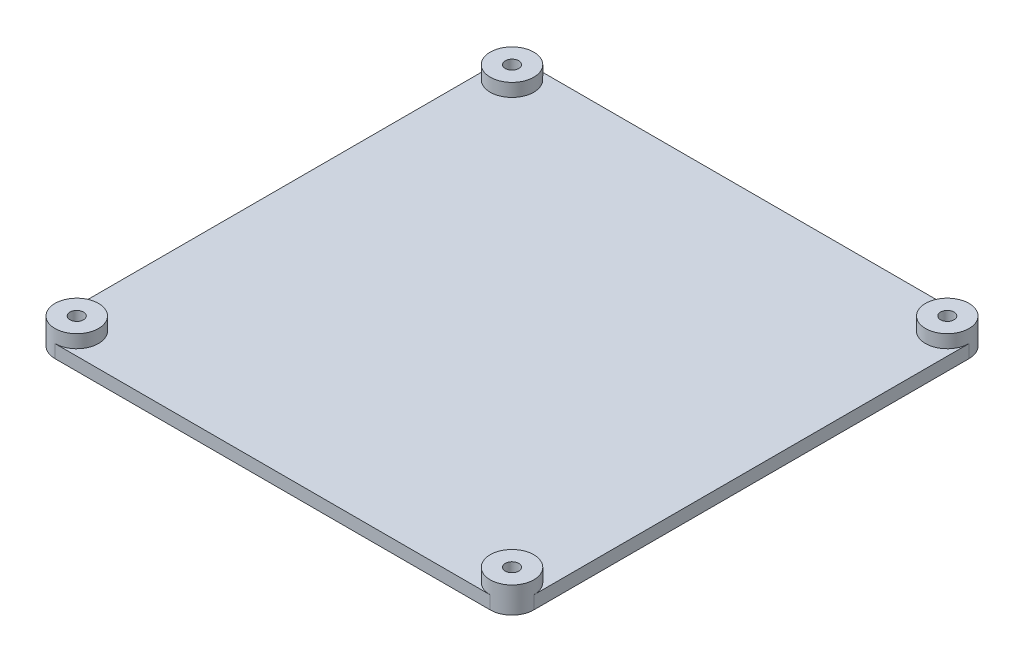
SolidWorks part; units mm, degrees
ref_plane "Front Plane" through (0, 0, 0) normal (0, 0, 1) x (1, 0, 0)
ref_plane "Top Plane" through (0, 0, 0) normal (0, 1, 0) x (1, 0, 0)
ref_plane "Right Plane" through (0, 0, 0) normal (1, 0, 0) x (0, 0, -1)
sketch "Sketch1" plane through (0, 0, 0) normal (0, 1, 0) x (1, 0, 0)
  line L1 (-55, 55) -> (55, 55)
  line L2 (-55, 55) -> (-55, -55)
  line L3 (-55, -55) -> (55, -55)
  line L4 (55, 55) -> (55, -55)
  point P0 (0, 0)
  dimension "D1" = 110
  dimension "D2" = 110
extrude "Boss-Extrude1" add sketch "Sketch1" along normal blind 3 contours L1 L4 L3 L2
fillet "Fillet1" radius 5 4 edges at (-55, 1.5, -55) (55, 1.5, -55) (55, 1.5, 55) (-55, 1.5, 55)
sketch "Sketch2" plane through (0, 3, 0) normal (0, 1, 0) x (1, 0, 0)
  circle A0 centre (-50, 50) radius 5
  circle A1 centre (50, 50) radius 5
  circle A2 centre (50, -50) radius 5
  circle A3 centre (-50, -50) radius 5
extrude "Boss-Extrude2" add sketch "Sketch2" along normal blind 3
sketch "Sketch6" plane through (0, 0, 0) normal (0, -1, 0) x (1, 0, 0)
  circle A0 centre (-50, 50) radius 1.55
  circle A1 centre (50, -50) radius 1.55
  circle A2 centre (50, 50) radius 1.55
  circle A3 centre (-50, -50) radius 1.55
  dimension "D1" = 3.1
  dimension "D2" = 3.1
  dimension "D3" = 3.1
  dimension "D4" = 3.1
extrude "Cut-Extrude1" cut sketch "Sketch6" against normal through all
